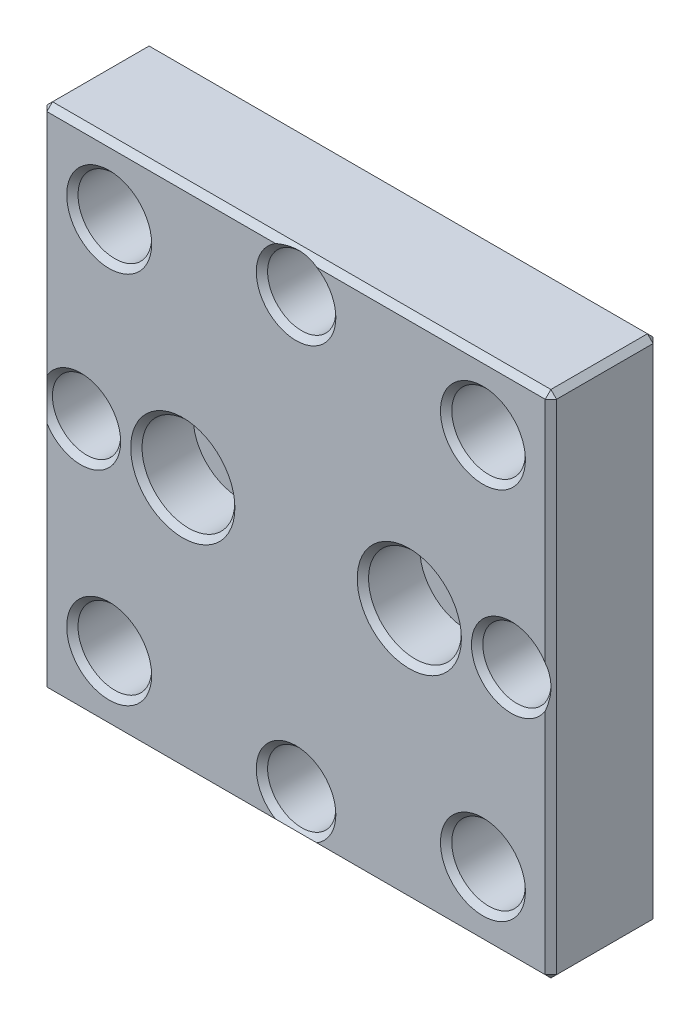
SolidWorks part; units mm, degrees
ref_plane "Front Plane" through (0, 0, 0) normal (0, 0, 1) x (1, 0, 0)
ref_plane "Top Plane" through (0, 0, 0) normal (0, 1, 0) x (1, 0, 0)
ref_plane "Right Plane" through (0, 0, 0) normal (1, 0, 0) x (0, 0, -1)
sketch "Sketch1" plane through (0, 0, 0) normal (0, 0, 1) x (1, 0, 0)
  line L1 (0, 0) -> (45, 0)
  line L2 (0, 0) -> (0, 45)
  line L3 (0, 45) -> (45, 45)
  line L4 (45, 0) -> (45, 45)
  circle A0 centre (22.5, 22.5) radius 15.125 construction
  circle A1 centre (12.5, 22.5) radius 2.2
  circle A2 centre (32.5, 22.5) radius 2.2
  circle A3 centre (12.5, 22.5) radius 4.1
  circle A4 centre (32.5, 22.5) radius 4.1
  dimension "D5" = 30.25
  dimension "D6" = 4.4
  dimension "D7" = 4.4
  dimension "D10" = 8.2
  dimension "D11" = 8.2
  dimension "D1" = 45
  dimension "D2" = 45
  dimension "D3" = 22.5
  dimension "D4" = 22.5
  dimension "D8" = 10
  dimension "D9" = 10
extrude "Boss-Extrude1" add sketch "Sketch1" along normal blind 9.525 contours L1 L4 L3 L2 A4 A3 region at (22.5, 22.5, 0)
extrude "Boss-Extrude2" add sketch "Sketch1<3>" along normal blind 4.5 contours A3 A1 | A4 A2 region at (8.516, 22.5, 0) region at (28.516, 22.5, 0)
sketch "Sketch1<3>" plane through (0, 0, 0) normal (0, 0, 1) x (1, 0, 0) same geometry as "Sketch1"
sketch "Sketch3" plane through (0, 0, 9.525) normal (0, 0, 1) x (1, 0, 0)
  line L0 (0, 45) -> (45, 45) construction
  line L1 (0, 0) -> (0, 45) construction
  line L2 (0, 0) -> (45, 0) construction
  line L3 (45, 0) -> (45, 45) construction
  circle A0 centre (22.5, 41.5) radius 3.0127
  circle A1 centre (3.5, 22.5) radius 3.0127
  circle A2 centre (41.5, 22.5) radius 3.0127
  circle A3 centre (22.5, 3.5) radius 3.0127
  dimension "D6" = 6.0254
  dimension "D7" = 6.0254
  dimension "D8" = 6.0254
  dimension "D9" = 6.0254
  dimension "D1" = 22.5
  dimension "D2" = 22.5
  dimension "D3" = 22.5
  dimension "D4" = 22.5
  dimension "D5" = 3.5
  dimension "D10" = 3.5
  dimension "D11" = 3.5
  dimension "D12" = 3.5
extrude "Cut-Extrude1" cut sketch "Sketch3" against normal through all
sketch "Sketch5" plane through (0, 0, 9.525) normal (0, 0, 1) x (1, 0, 0)
  line L0 (0, 45) -> (45, 45) construction
  line L1 (0, 0) -> (0, 45) construction
  circle A0 centre (6, 39) radius 3.2512
  circle A1 centre (39, 39) radius 3.2512
  circle A2 centre (39, 6) radius 3.2512
  circle A3 centre (6, 6) radius 3.2512
  dimension "D1" = 6.5024
  dimension "D2" = 6.5024
  dimension "D3" = 6.5024
  dimension "D4" = 6.5024
  dimension "D5" = 6
  dimension "D6" = 6
  dimension "D7" = 33
  dimension "D8" = 33
extrude "Cut-Extrude2" cut sketch "Sketch5" against normal blind 6.4008
sketch "Sketch6" plane through (0, 0, 9.525) normal (0, 0, 1) x (1, 0, 0)
  line L1 (0, 0) -> (0, 45) construction
  circle A0 centre (6, 39) radius 1.25
  circle A1 centre (39, 39) radius 1.25
  circle A2 centre (39, 6) radius 1.25
  circle A3 centre (6, 6) radius 1.25
  dimension "D1" = 2.5
  dimension "D2" = 2.5
  dimension "D3" = 2.5
  dimension "D4" = 2.5
  dimension "D5" = 33
  dimension "D6" = 6
  dimension "D7" = 33
  dimension "D8" = 33
  dimension "D9" = 33
  dimension "D10" = 6
extrude "Cut-Extrude3" cut sketch "Sketch6" against normal through all
sketch "Sketch7" plane through (0, 0, 0) normal (0, 0, -1) x (-1, 0, 0)
  line L0 (0, 0) -> (-45, 0) construction
  line L1 (-13.65, 22.5) -> (-31.35, 22.5)
  line L2 (-13.65, 22.5) -> (-13.65, -17.5)
  line L3 (-13.65, -17.5) -> (-31.35, -17.5)
  line L4 (-31.35, 22.5) -> (-31.35, -17.5)
  circle A0 centre (-22.5, 22.5) radius 15.3
  circle A1 centre (-3.5, 22.5) radius 3.0127 construction
  circle M15 centre (-22.5, 3.5) radius 3.0127
  line M19 (-45, 0) -> (0, 0)
  line M22 (-45, 45) -> (-45, 0)
  circle M23 centre (-12.5, 22.5) radius 2.2
  circle M24 centre (-32.5, 22.5) radius 2.2
  circle M27 centre (-39, 6) radius 1.25
  dimension "D1" = 30.6
  dimension "D2" = 22.5
  dimension "D3" = 22.5
  dimension "D4" = 17.7
  dimension "D5" = 40
  dimension "D6" = 8.85
  dimension "D7" = 40
  dimension "D8" = 90
extrude "Cut-Extrude4" cut sketch "Sketch7" against normal blind 3.5 contours A0 L4 L2 M22 M19 M27 | L4 A0 L2 L1 M24 | L2 A0 L4 L1 M24 M23 | A0 L4 L2 M19 M15 region at (22.5, 26.5592, 0) region at (22.5, 15.2056, 0) region at (22.5, 6.9966, 0)
chamfer "Chamfer1" distance 0.5 angle 45 37 edges at (36.6, 22.5, 9.525) (16.6, 22.5, 9.525) (6.5127, 22.5, 9.525) (9.2512, 6, 9.525) (42.2512, 6, 9.525) (44.5127, 22.5, 9.525) (42.2512, 39, 9.525) (25.5127, 41.5, 9.525) (9.2512, 39, 9.525) (7.25, 39, 0) (40.25, 39, 0) (40.25, 6, 0) (44.5127, 22.5, 0) (19.4873, 3.5, 3.5) (7.25, 6, 0) (6.5127, 22.5, 0) (25.5127, 41.5, 0) (45, 22.5, 9.525) (22.5, 45, 9.525) (45, 45, 4.7625) (45, 0, 4.7625) (22.5, 0, 9.525) (0, 22.5, 9.525) (0, 45, 4.7625) (0, 0, 4.7625) (0, 22.5, 0) (22.5, 45, 0) (45, 22.5, 0) (31.35, 0, 1.75) (22.5, 0, 3.5) (13.65, 0, 1.75) (6.825, 0, 0) (38.175, 0, 0) (31.35, 5.0097, 0) (13.65, 5.0097, 0) (22.5, 37.8, 0) (25.5127, 3.5, 9.525)
